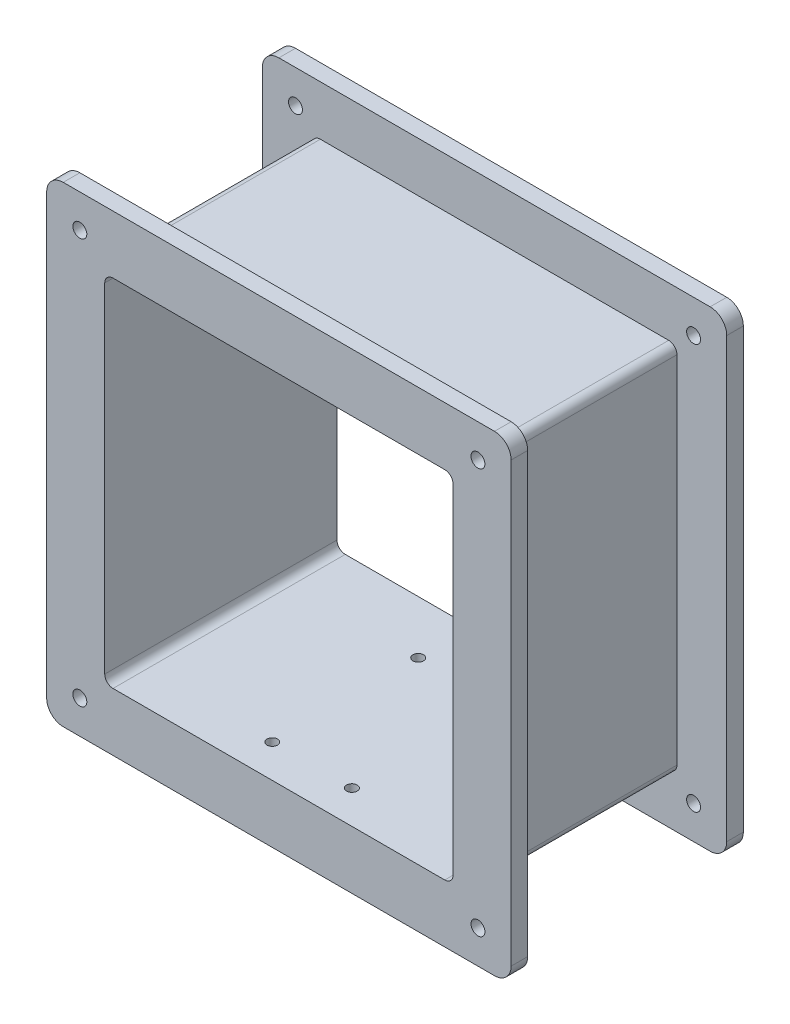
SolidWorks part; units mm, degrees
ref_plane "前视基准面" through (0, 0, 0) normal (0, 0, 1) x (1, 0, 0)
ref_plane "上视基准面" through (0, 0, 0) normal (0, 1, 0) x (1, 0, 0)
ref_plane "右视基准面" through (0, 0, 0) normal (1, 0, 0) x (0, 0, -1)
sketch "草图4" plane through (0, 0, 0) normal (0, 0, 1) x (1, 0, 0)
  line L1 (-105, -107.125) -> (105, -107.125)
  line L2 (-105, -107.125) -> (-105, 107.125)
  line L3 (-105, 107.125) -> (105, 107.125)
  line L4 (105, -107.125) -> (105, 107.125)
  line L5 (-105, -107.125) -> (105, 107.125) construction
  line L6 (-105, 107.125) -> (105, -107.125) construction
  line L7 (-110, -112.125) -> (110, -112.125)
  line L8 (-110, -112.125) -> (-110, 112.125)
  line L9 (-110, 112.125) -> (110, 112.125)
  line L10 (110, -112.125) -> (110, 112.125)
  line L11 (-110, -112.125) -> (110, 112.125) construction
  line L12 (-110, 112.125) -> (110, -112.125) construction
  point P0 (0, 0)
  point P6 (0, 0)
  dimension "D1" = 210
  dimension "D2" = 214.25
  dimension "D3" = 5
  dimension "D4" = 5
extrude "凸台-拉伸7" add sketch "草图4" along normal blind 120
sketch "草图7" plane through (0, 0, 0) normal (0, 0, -1) x (-1, 0, 0)
  line L0 (-110, 112.125) -> (110, 112.125) construction
  line L1 (140, 142.125) -> (-140, 142.125)
  line L2 (140, 142.125) -> (140, -142.125)
  line L3 (140, -142.125) -> (-140, -142.125)
  line L4 (-140, 142.125) -> (-140, -142.125)
  line L5 (140, 142.125) -> (-140, -142.125) construction
  line L6 (140, -142.125) -> (-140, 142.125) construction
  line L7 (-110, -112.125) -> (-110, 112.125) construction
  line L8 (105, -107.125) -> (-105, -107.125) construction
  line L9 (105, 107.125) -> (105, -107.125) construction
  line L10 (-105, 107.125) -> (105, 107.125) construction
  line L11 (-105, -107.125) -> (-105, 107.125) construction
  line L12 (105, -107.125) -> (-105, -107.125)
  line L13 (105, 107.125) -> (105, -107.125)
  line L14 (-105, 107.125) -> (105, 107.125)
  line L15 (-105, -107.125) -> (-105, 107.125)
  point P0 (0, 0)
  dimension "D1" = 30
  dimension "D2" = 30
extrude "凸台-拉伸8" add sketch "草图7" along normal blind 10
sketch "草图8" plane through (0, 0, 120) normal (0, 0, 1) x (1, 0, 0)
  line L1 (140, -142.125) -> (-140, -142.125)
  line L2 (140, -142.125) -> (140, 142.125)
  line L3 (140, 142.125) -> (-140, 142.125)
  line L4 (-140, -142.125) -> (-140, 142.125)
  line L5 (140, -142.125) -> (-140, 142.125) construction
  line L6 (140, 142.125) -> (-140, -142.125) construction
  line L7 (105, -107.125) -> (105, 107.125) construction
  line L8 (-105, -107.125) -> (105, -107.125) construction
  line L9 (-105, 107.125) -> (-105, -107.125) construction
  line L10 (105, 107.125) -> (-105, 107.125) construction
  line L11 (105, -107.125) -> (105, 107.125)
  line L12 (-105, -107.125) -> (105, -107.125)
  line L13 (-105, 107.125) -> (-105, -107.125)
  line L14 (105, 107.125) -> (-105, 107.125)
  point P0 (0, 0)
extrude "凸台-拉伸9" add sketch "草图8" along normal blind 10
fillet "圆角5" radius 5 8 edges at (-105, 107.125, 60) (-110, 112.125, 60) (105, -107.125, 60) (110, -112.125, 60) (-105, -107.125, 60) (-110, -112.125, 60) (110, 112.125, 60) (105, 107.125, 60)
fillet "圆角6" radius 10 8 edges at (140, 142.125, 125) (140, -142.125, 125) (-140, -142.125, 125) (-140, 142.125, 125) (-140, 142.125, -5) (-140, -142.125, -5) (140, -142.125, -5) (140, 142.125, -5)
hole_wizard "Ø8.4 (8.4) 直径孔1" positions "草图16" profile "草图17" hole size "Ø8.4" standard "GB" end condition through all
sketch "草图16" plane through (0, 0, -10) normal (0, 0, -1) x (-1, 0, 0)
  line L0 (130, 142.125) -> (-130, 142.125) construction
  line L1 (-140, 132.125) -> (-140, -132.125) construction
  line L2 (140, -132.125) -> (140, 132.125) construction
  line L3 (-130, -142.125) -> (130, -142.125) construction
  point P0 (120, -122.125)
  point P3 (120, 122.125)
  point P6 (-120, 122.125)
  point P9 (-120, -122.125)
  dimension "D1" = 20
  dimension "D2" = 20
  dimension "D3" = 20
  dimension "D4" = 20
  dimension "D5" = 20
  dimension "D6" = 20
  dimension "D7" = 20
  dimension "D8" = 20
sketch "草图17" plane through (-120, -122.125, -10) normal (1, 0, 0) x (0, 1, 0)
  line L0 (0, 0) -> (0, 140)
  line L1 (0, 140) -> (4.2, 140)
  line L2 (4.2, 140) -> (4.2, 0)
  line L5 (4.2, 0) -> (0, 0)
  line L11 (0, -6.35) -> (0, 107.95) construction
  dimension "通孔孔直径" = 8.4
  dimension "通孔孔深度" = 140
sketch "草图18" plane through (0, -112.125, 0) normal (0, -1, 0) x (1, 0, 0)
  line L0 (-130, 130) -> (130, 130) construction
  line L5 (105, 0) -> (105, 120) construction
  point P0 (-24, 110)
  point P1 (-24, 22)
  point P2 (24, 22)
  point P3 (24, 110)
  dimension "D1" = 48
  dimension "D2" = 48
  dimension "D3" = 88
  dimension "D4" = 88
  dimension "D5" = 100.2397
  dimension "D6" = 20
  dimension "D7" = 20
  dimension "D8" = 81
hole_wizard "Ø6.4 (6.4) 直径孔1" positions "草图21" profile "草图22" hole size "Ø6.4" standard "GB" end condition up to next
sketch "草图21" plane through (0, -112.125, 0) normal (0, -1, 0) x (-1, 0, 0)
  point P0 (24, -110)
  point P3 (-24, -110)
  point P6 (-24, -22)
  point P9 (24, -22)
sketch "草图22" plane through (-24, -112.125, 110) normal (1, 0, 0) x (0, 0, -1)
  line L0 (0, 0) -> (0, 5)
  line L1 (0, 5) -> (3.2, 5)
  line L2 (3.2, 5) -> (3.2, 0)
  line L5 (3.2, 0) -> (0, 0)
  line L11 (0, -6.35) -> (0, 107.95) construction
  dimension "通孔孔直径" = 6.4
  dimension "通孔孔深度" = 5
